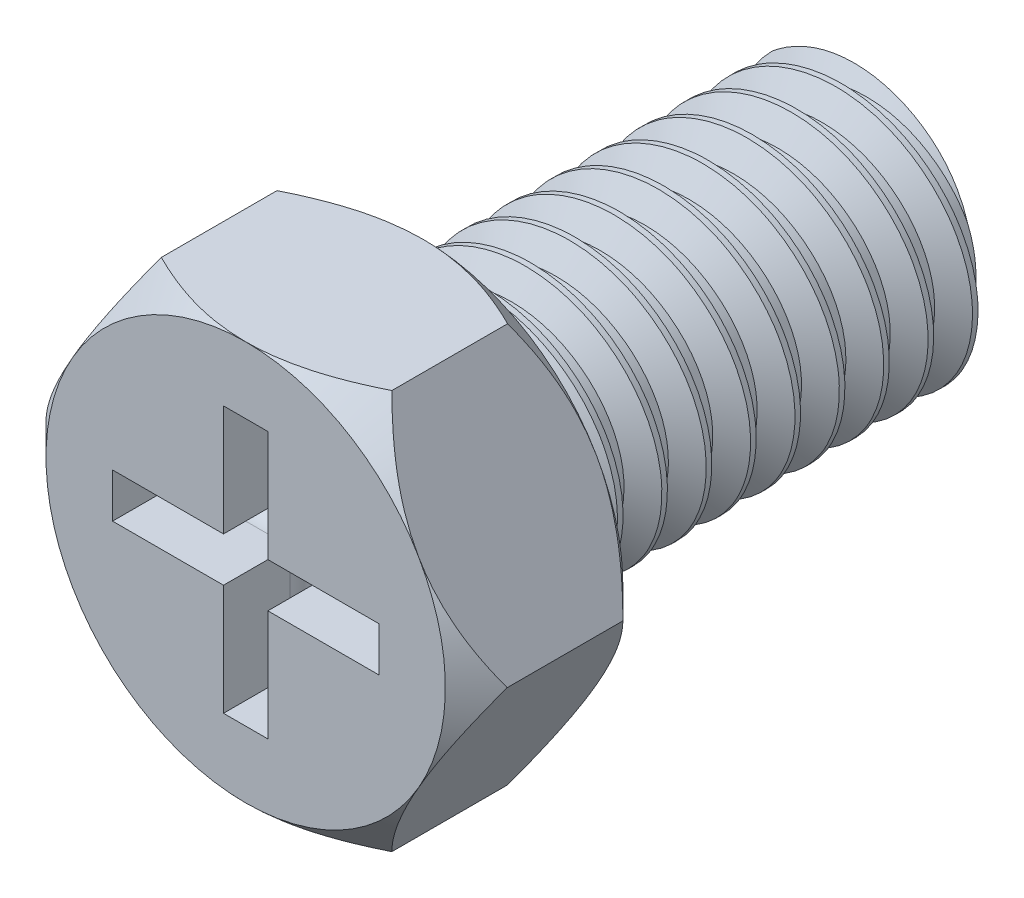
SolidWorks part; units mm, degrees
ref_plane "Front Plane" through (0, 0, 0) normal (0, 0, 1) x (1, 0, 0)
ref_plane "Top Plane" through (0, 0, 0) normal (0, 1, 0) x (1, 0, 0)
ref_plane "Right Plane" through (0, 0, 0) normal (1, 0, 0) x (0, 0, -1)
sketch "Sketch1" plane through (0, 0, 0) normal (0, 0, 1) x (1, 0, 0)
  line L0 (-2.5981, 0) -> (2.5981, 0) construction
  line L1 (2.5981, 0) -> (1.299, 2.25)
  line L2 (1.299, 2.25) -> (-1.299, 2.25)
  line L3 (-1.299, 2.25) -> (-2.5981, 0)
  line L4 (-2.5981, 0) -> (-1.299, -2.25)
  line L5 (-1.299, -2.25) -> (1.299, -2.25)
  line L6 (1.299, -2.25) -> (2.5981, 0)
  line L7 (0, 2.25) -> (0, -2.25) construction
  circle A0 centre (0, 0) radius 2.25
  circle A1 centre (0, 0) radius 1.5
  dimension "D1" = 4.5
  dimension "D2" = 3
extrude "Boss-Extrude1" add sketch "Sketch1" along normal blind 2 contours L1 L2 L3 L4 L5 L6
extrude "Boss-Extrude2" add sketch "Sketch1<3>" along normal up to next (2 mm away) and the other way blind 5 contours A1
sketch "Sketch1<3>" plane through (0, 0, 0) normal (0, 0, 1) x (1, 0, 0) same geometry as "Sketch1"
thread "Thread1" pitch 0.5 method cut profile "Thread Profile2" start angle 0, offset 0, length 0, pitch 0.5, diameter 3
ref_plane "Plane2" through (-1.5, 0, 0) normal (0, -1, 0) x (-1, 0, 0)
sketch "Thread Profile2" plane through (-1.5, 0, 0) normal (0, -1, 0) x (-1, 0, 0)
  line L0 (0, 0) -> (0, 0.5) construction
  line L11 (0, 0) -> (0, 0.4375)
  line L12 (0, 0.4375) -> (-0.2706, 0.2812)
  line L13 (-0.2706, 0.2812) -> (-0.2706, 0.1562)
  line L15 (-0.2706, 0.1562) -> (0, 0)
  line L17 (-0.2706, 0.2187) -> (0, 0.2187) construction
  point P2 (0, 0)
  dimension "Pitch" = 0.5
  dimension "Profile_Angle" = 60
  dimension "Profile_Land" = 0.125
  dimension "Profile_Height" = 0.2706
extrude "Cut-Extrude3" cut sketch "Sketch1<8>" along normal blind 1 draft 45 flip side to cut contours A0
sketch "Sketch1<8>" plane through (0, 0, 0) normal (0, 0, 1) x (1, 0, 0) same geometry as "Sketch1"
ref_plane "Plane3" through (0, 0, 2) normal (0, 0, 1) x (1, 0, 0)
sketch "Sketch8" plane through (0, 0, 2) normal (0, 0, 1) x (1, 0, 0)
  circle A0 centre (0, 0) radius 2.25
  dimension "D1" = 4.5
extrude "Cut-Extrude4" cut sketch "Sketch8" against normal blind 1 draft 45 flip side to cut contours A0
ref_plane "Plane4" through (0, 0, -5) normal (0, 0, -1) x (-1, 0, 0)
sketch "Sketch9" plane through (0, 0, -5) normal (0, 0, -1) x (-1, 0, 0)
  line L0 (-2.5981, 0) -> (2.5981, 0) construction
  line L1 (0, 2.25) -> (0, -2.25) construction
  line L2 (-1.299, 2.25) -> (1.299, 2.25) construction
ref_plane "Plane5" through (0, 0, 2) normal (0, 0, 1) x (1, 0, 0)
sketch "Sketch10" plane through (0, 0, 2) normal (0, 0, 1) x (1, 0, 0)
  line L0 (0, 1.5) -> (0, -1.5) construction
  line L1 (1.5, 0) -> (-1.5, 0) construction
  line L2 (-0.25, -1.5) -> (0.25, -1.5)
  line L3 (0.25, -1.5) -> (0.25, -0.25)
  line L4 (0.25, -0.25) -> (1.5, -0.25)
  line L5 (1.5, -0.25) -> (1.5, 0.25)
  line L6 (1.5, 0.25) -> (0.25, 0.25)
  line L7 (0.25, 0.25) -> (0.25, 1.5)
  line L8 (0.25, 1.5) -> (-0.25, 1.5)
  line L9 (-0.25, 1.5) -> (-0.25, 0.25)
  line L10 (-0.25, 0.25) -> (-1.5, 0.25)
  line L12 (-1.5, 0.25) -> (-1.5, -0.25)
  line L13 (-1.5, -0.25) -> (-0.25, -0.25)
  line L14 (-0.25, -0.25) -> (-0.25, -1.5)
  point P5 (0, 0)
  point P10 (0, 0)
  dimension "D1" = 3
  dimension "D2" = 3
  dimension "D3" = 0.5
  dimension "D4" = 0.5
  dimension "D5" = 0.5
  dimension "D6" = 0.5
  dimension "D7" = 0.5
  dimension "D8" = 1.25
  dimension "D9" = 1.25
  dimension "D10" = 1.25
extrude "Cut-Extrude5" cut sketch "Sketch10" against normal blind 1
fillet "Fillet1" radius 0.25 12 edges at (-0.875, -0.25, 1) (-1.5, 0, 1) (-0.875, 0.25, 1) (-0.25, 0.875, 1) (0, 1.5, 1) (0.25, 0.875, 1) (0.875, 0.25, 1) (1.5, 0, 1) (0.875, -0.25, 1) (0.25, -0.875, 1) (0, -1.5, 1) (-0.25, -0.875, 1)
equation "\"D1@Sketch8\"= \"D1@Sketch1\""
